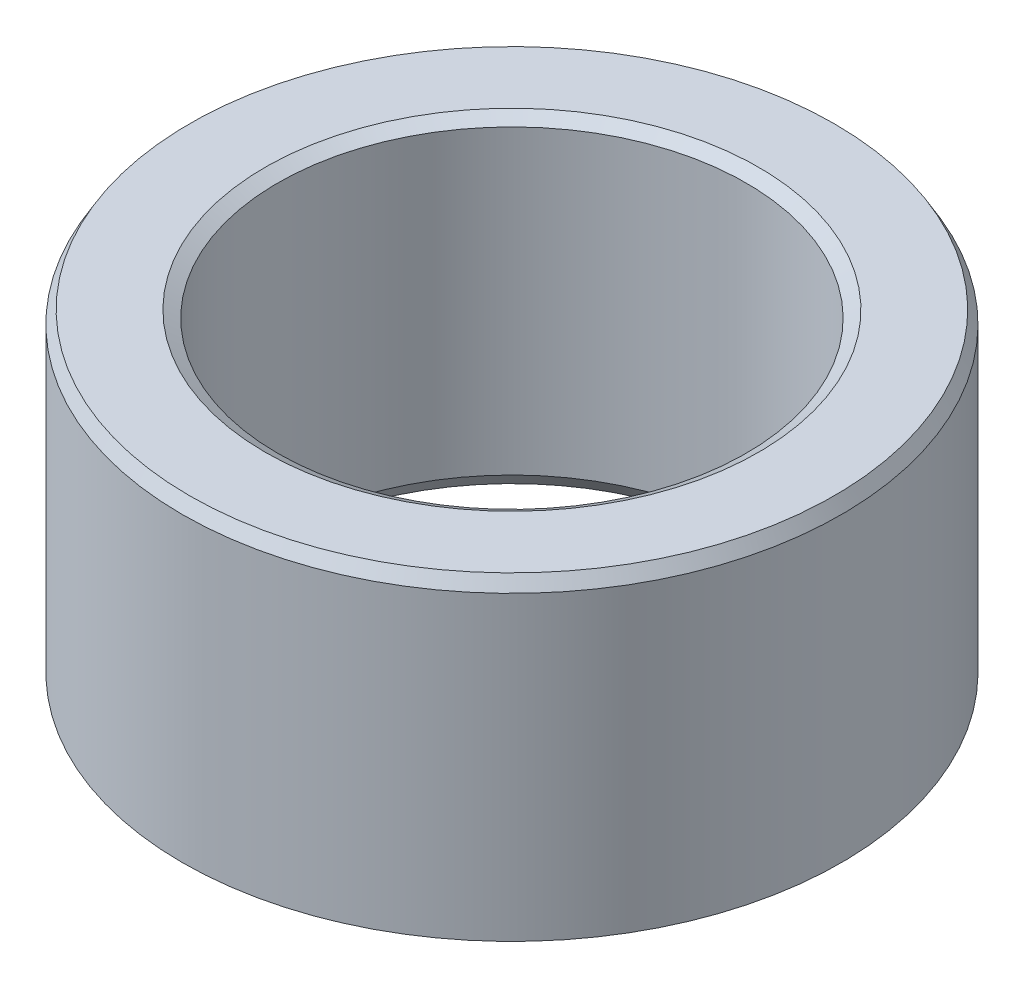
SolidWorks part; units mm, degrees
ref_plane "Front Plane" through (0, 0, 0) normal (0, 0, 1) x (1, 0, 0)
ref_plane "Top Plane" through (0, 0, 0) normal (0, 1, 0) x (1, 0, 0)
ref_plane "Right Plane" through (0, 0, 0) normal (1, 0, 0) x (0, 0, -1)
sketch "Sketch1" plane through (0, 0, 0) normal (0, 1, 0) x (1, 0, 0)
  circle A0 centre (0, 0) radius 60
  dimension "SLEEVE_OD" = 120
extrude "Boss-Extrude1" add sketch "Sketch1" along normal blind 58.4986
sketch "Sketch2" plane through (0, 0, 0) normal (0, 1, 0) x (1, 0, 0)
  circle A0 centre (0, 0) radius 42.6383
  dimension "BORE_D" = 85.2766
extrude "Cut-Extrude1" cut sketch "Sketch2" along normal through all
chamfer "Chamfer1" distance 2.2942 angle 30 4 edges at (0, 58.4986, 42.6383) (0, 0, 42.6383) (0, 0, 60) (0, 58.4986, 60) first distance on face at (0, 58.4986, 42.6383) first distance on face at (0, 0, 42.6383) first distance on face at (0, 58.4986, 60)
